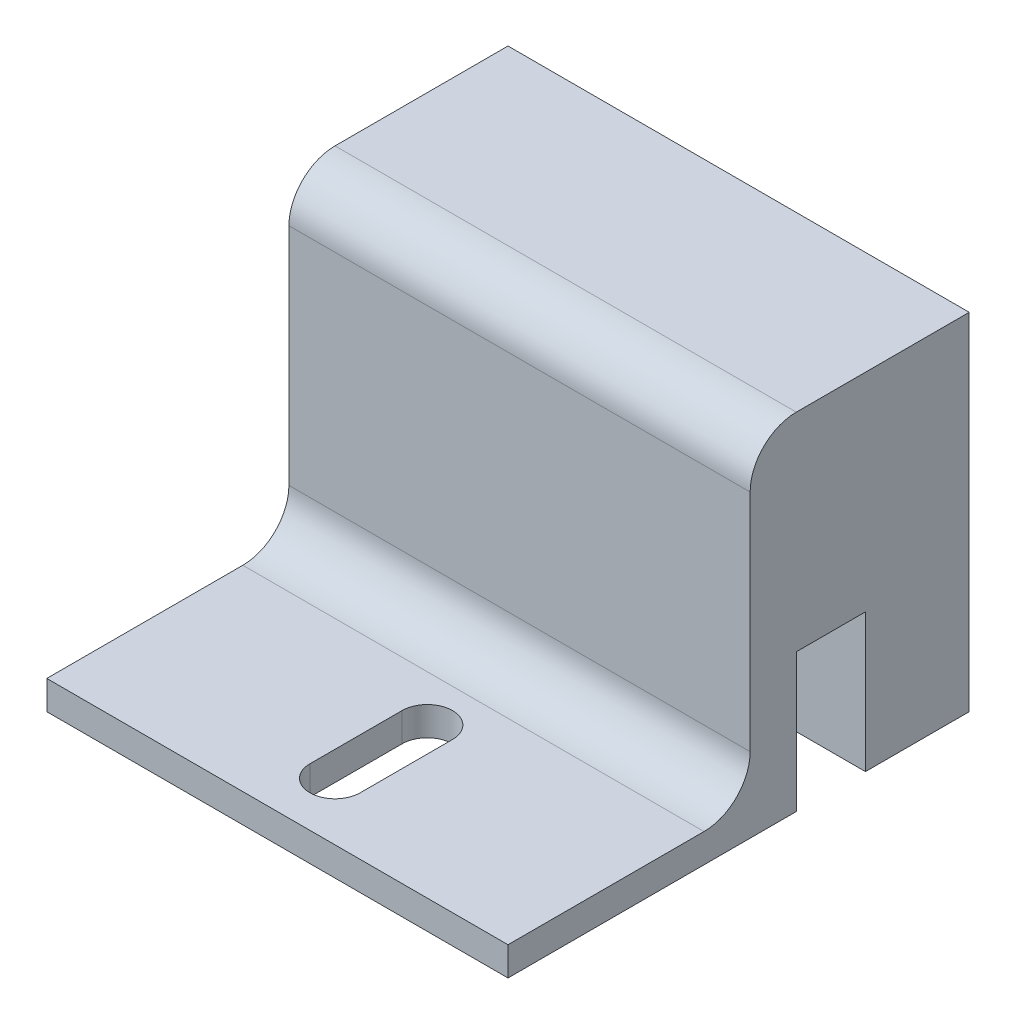
SolidWorks part; units mm, degrees
ref_plane "Front Plane" through (0, 0, 0) normal (0, 0, 1) x (1, 0, 0)
ref_plane "Top Plane" through (0, 0, 0) normal (0, 1, 0) x (1, 0, 0)
ref_plane "Right Plane" through (0, 0, 0) normal (1, 0, 0) x (0, 0, -1)
sketch "Sketch1" plane through (0, 0, 0) normal (1, 0, 0) x (0, 0, -1)
  line L0 (0, 0) -> (-11.43, 0)
  line L1 (-11.43, 0) -> (-11.43, 15.24)
  line L2 (-11.43, 15.24) -> (-19.05, 15.24)
  line L3 (-19.05, 15.24) -> (-19.05, 0)
  line L4 (-19.05, 0) -> (-50.8, 0)
  line L5 (-50.8, 0) -> (-50.8, 3.175)
  line L6 (-50.8, 3.175) -> (-24.13, 3.175)
  line L9 (-24.13, 3.175) -> (-24.13, 38.1)
  line L10 (-24.13, 38.1) -> (0, 38.1)
  line L11 (0, 38.1) -> (0, 0)
  dimension "D1" = 38.1
  dimension "D2" = 11.43
  dimension "D3" = 7.62
  dimension "D4" = 3.175
  dimension "D5" = 5.08
  dimension "D6" = 50.8
  dimension "D7" = 15.24
extrude "Boss-Extrude1" add sketch "Sketch1" along normal blind 50.8
sketch "Sketch2" plane through (0, 3.175, 0) normal (0, 1, 0) x (1, 0, 0)
  line L0 (25.4, -34.29) -> (25.4, -44.45) construction
  line L1 (28.1686, -34.29) -> (28.1686, -44.45)
  line L2 (22.6314, -34.29) -> (22.6314, -44.45)
  line L3 (50.8, -50.8) -> (0, -50.8) construction
  arc A0 (28.1686, -34.29) -> (22.6314, -34.29) centre (25.4, -34.29) ccw
  arc A1 (22.6314, -44.45) -> (28.1686, -44.45) centre (25.4, -44.45) ccw
  point P2 (25.4, -39.37)
  point P10 (25.4, -50.8)
  dimension "D1" = 5.5372
  dimension "D2" = 10.16
  dimension "D3" = 6.35
extrude "Cut-Extrude1" cut sketch "Sketch2" against normal through all
fillet "Fillet1" radius 5.08 2 edges at (25.4, 38.1, 24.13) (25.4, 3.175, 24.13)
